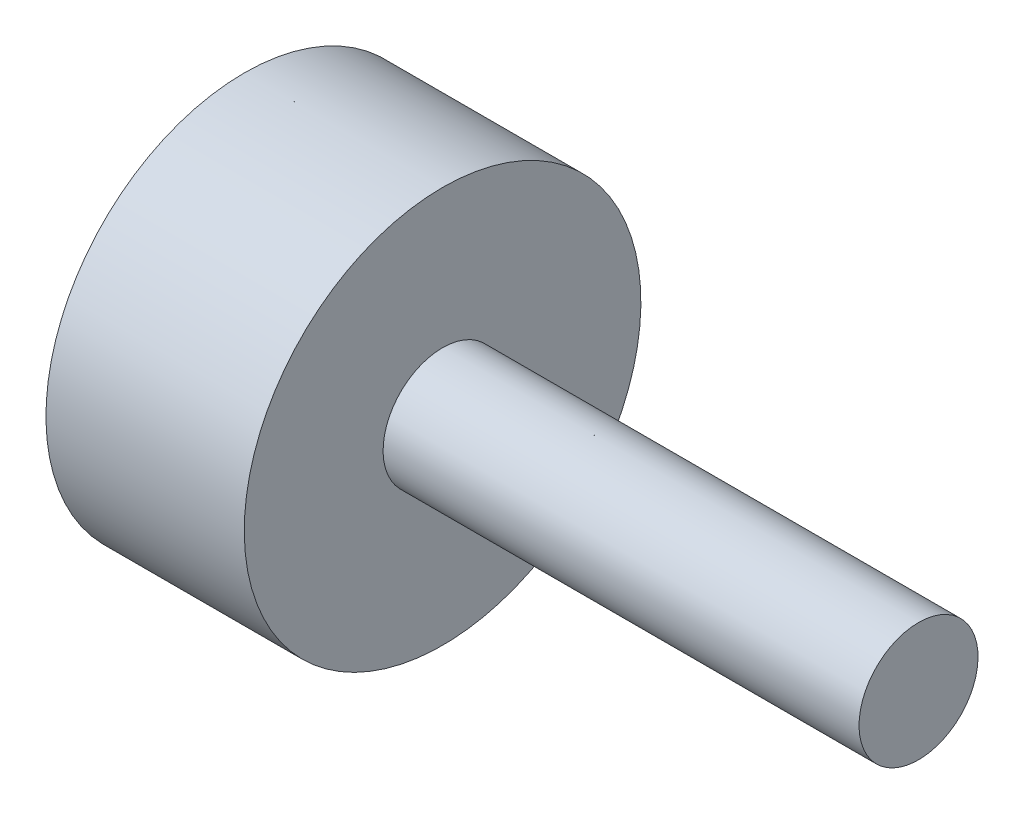
SolidWorks part; units mm, degrees
ref_plane "Front Plane" through (0, 0, 0) normal (0, 0, 1) x (1, 0, 0)
ref_plane "Top Plane" through (0, 0, 0) normal (0, 1, 0) x (1, 0, 0)
ref_plane "Right Plane" through (0, 0, 0) normal (1, 0, 0) x (0, 0, -1)
sketch "Sketch1" plane through (0, 0, 0) normal (0, 0, 1) x (1, 0, 0)
  line L0 (0, 0) -> (17, 0) construction
  line L1 (0, 0) -> (0, 5)
  line L2 (0, 5) -> (5, 5)
  line L3 (5, 5) -> (5, 1.5)
  line L4 (5, 1.5) -> (17, 1.5)
  line L5 (17, 1.5) -> (17, 0)
  line L6 (17, 0) -> (0, 0)
revolve "Revolve1" add sketch "Sketch1" angle 360 about L0
